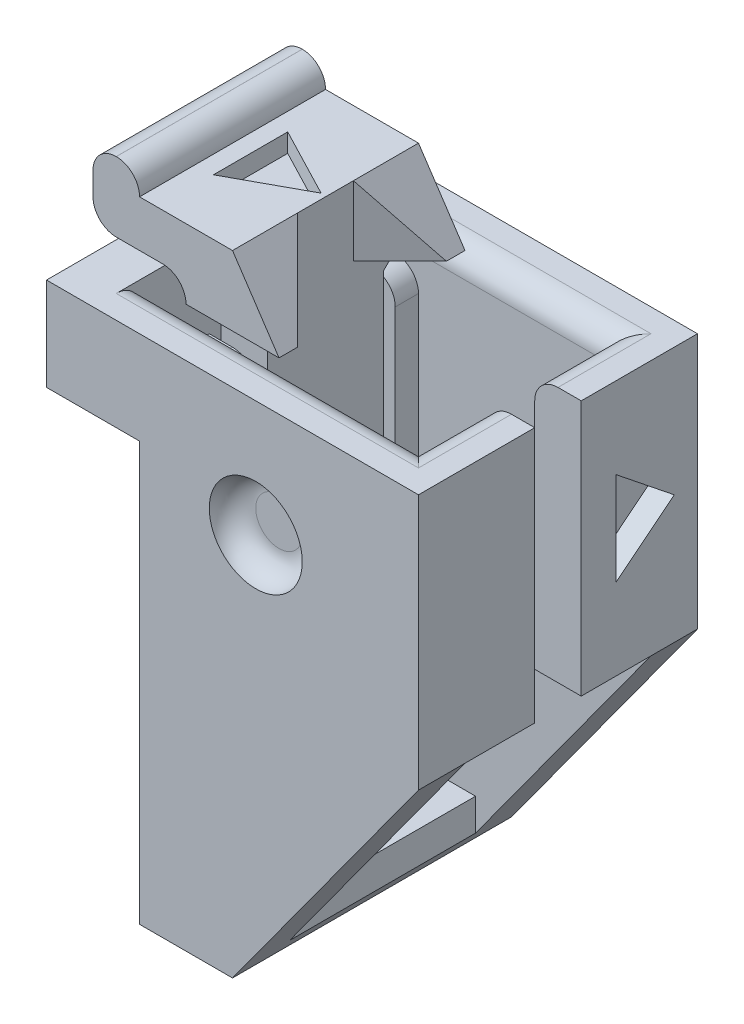
SolidWorks part; units mm, degrees
ref_plane "Front Plane" through (0, 0, 0) normal (0, 0, 1) x (1, 0, 0)
ref_plane "Top Plane" through (0, 0, 0) normal (0, 1, 0) x (1, 0, 0)
ref_plane "Right Plane" through (0, 0, 0) normal (1, 0, 0) x (0, 0, -1)
sketch "BaseSketch" plane through (0, 0, 0) normal (0, 1, 0) x (1, 0, 0)
  line L1 (-6.2677, 3.9685) -> (9.7323, 3.9685)
  line L2 (-6.2677, 3.9685) -> (-6.2677, -8.0315)
  line L3 (-6.2677, -8.0315) -> (9.7323, -8.0315)
  line L4 (9.7323, 3.9685) -> (9.7323, -8.0315)
  dimension "D1" = 16
  dimension "D2" = 12
extrude "BaseExtrude" add sketch "BaseSketch" along normal blind 2
sketch "SlotSketch" plane through (0, 2, 0) normal (0, 1, 0) x (1, 0, 0)
  line L10 (-2.2677, 0.9685) -> (-0.2677, 0.9685)
  line L11 (-2.2677, 1.9685) -> (-4.2677, 1.9685)
  line L12 (-2.2677, 1.9685) -> (-2.2677, 0.9685)
  line L13 (-0.2677, -6.0315) -> (7.7323, -6.0315)
  line L14 (7.7323, -6.0315) -> (7.7323, 1.9685)
  line L15 (-4.2677, -6.0315) -> (7.7323, -6.0315)
  line L16 (-4.2677, 1.9685) -> (-4.2677, -6.0315)
  line L17 (7.7323, 1.9685) -> (-4.2677, 1.9685)
  line L18 (7.7323, -6.0315) -> (7.7323, 1.9685)
  line L19 (-4.2677, -6.0315) -> (-2.2677, -6.0315)
  line L20 (-4.2677, 1.9685) -> (-4.2677, -6.0315)
  line L21 (7.7323, 1.9685) -> (-0.2677, 1.9685)
  line L22 (-0.2677, 1.9685) -> (-0.2677, 0.9685)
  line L23 (-2.2677, -5.0315) -> (-0.2677, -5.0315)
  line L24 (-2.2677, 0.4685) -> (-2.2677, -4.5315)
  line L25 (-2.2677, 0.4685) -> (-0.2677, 0.4685)
  line L26 (-2.2677, 0.4685) -> (-2.2677, -4.5315)
  line L27 (-2.2677, -4.5315) -> (-0.2677, -4.5315)
  line L28 (-0.2677, 0.4685) -> (-0.2677, -4.5315)
  line L29 (-0.2677, 0.4685) -> (-0.2677, -4.5315)
  line L30 (-2.2677, -5.0315) -> (-2.2677, -6.0315)
  line L31 (-0.2677, -5.0315) -> (-0.2677, -6.0315)
  line L33 (-6.2677, 3.9685) -> (9.7323, 3.9685)
  line L34 (-6.2677, 3.9685) -> (-6.2677, -8.0315)
  line L35 (-6.2677, -8.0315) -> (9.7323, -8.0315)
  line L36 (9.7323, 3.9685) -> (9.7323, -8.0315)
  line M5 (-6.2677, 3.9685) -> (-6.2677, -8.0315)
  line M6 (-6.2677, -8.0315) -> (9.7323, -8.0315)
  line M7 (9.7323, -8.0315) -> (9.7323, 3.9685)
  line M8 (9.7323, 3.9685) -> (-6.2677, 3.9685)
  dimension "D2" = 8
  dimension "D3" = 2
  dimension "D4" = 2
  dimension "D5" = 8
  dimension "D6" = 1
  dimension "D7" = 1
  dimension "D8" = 5
  dimension "D9" = 0.5
  dimension "D1" = 2
extrude "FlapExtrude" add sketch "SlotSketch" along normal blind 20.1 contours L25 L28 L27 L24
sketch "HandleBaseSketch" plane through (0, 22.1, 0) normal (0, 1, 0) x (1, 0, 0)
  line L0 (9.7323, 3.9685) -> (-6.2677, 3.9685) construction
  line L1 (-2.2677, 1.9685) -> (-0.2677, 1.9685)
  line L2 (-2.2677, 1.9685) -> (-2.2677, -6.0315)
  line L3 (-2.2677, -6.0315) -> (-0.2677, -6.0315)
  line L4 (-0.2677, 1.9685) -> (-0.2677, -6.0315)
  line L5 (-6.2677, -8.0315) -> (9.7323, -8.0315) construction
  dimension "D1" = 2
  dimension "D2" = 2
extrude "HandleBase" add sketch "HandleBaseSketch" along normal blind 3
sketch "TriangleBaseSketch" plane through (-0.2677, 0, 0) normal (1, 0, 0) x (0, 0, -1)
  line L0 (-6.0315, 22.1) -> (-3.2315, 22.1)
  line L1 (-3.2315, 22.1) -> (-3.2315, 25.1)
  line L2 (-6.0315, 25.1) -> (1.9685, 25.1) construction
  line L3 (-3.2315, 25.1) -> (-6.0315, 25.1)
  line L4 (-6.0315, 25.1) -> (-6.0315, 22.1)
  line L5 (1.9685, 22.1) -> (-0.8315, 22.1)
  line L6 (-0.8315, 22.1) -> (-0.8315, 25.1)
  line L7 (-0.8315, 25.1) -> (1.9685, 25.1)
  line L8 (1.9685, 25.1) -> (1.9685, 22.1)
extrude "PyramidExtrude" add sketch "TriangleBaseSketch" along normal blind 2.8
sketch "PyramidSideCutSketch" plane through (0, 0, -1.9685) normal (0, 0, -1) x (-1, 0, 0)
  line L0 (0.2677, 25.1) -> (0.2677, 22.1)
  line L1 (0.2677, 25.1) -> (-2.5323, 25.1)
  line L2 (-2.5323, 25.1) -> (-2.5323, 22.1)
  line L3 (-2.5323, 22.1) -> (-1.7323, 22.1)
  line L4 (-2.5323, 22.1) -> (2.2677, 22.1) construction
  line L5 (-1.7323, 22.1) -> (0.2677, 25.1)
  dimension "D1" = 2
sketch "PyramidTopCutSketch" plane through (0, 25.1, 0) normal (0, 1, 0) x (1, 0, 0)
  line L0 (-0.2677, -3.2315) -> (2.5323, -6.0315)
  line L1 (2.5323, -6.0315) -> (2.5323, -3.2315)
  line L2 (2.5323, -3.2315) -> (-0.2677, -3.2315)
  line L3 (-0.2677, -0.8315) -> (2.5323, 1.9685)
  line L4 (2.5323, 1.9685) -> (2.5323, -0.8315)
  line L5 (2.5323, -0.8315) -> (-0.2677, -0.8315)
extrude "PyramidTopCut" cut sketch "PyramidTopCutSketch" against normal blind 3
extrude "PyramidSideCut" cut sketch "PyramidSideCutSketch" against normal through all contours L1 L2 L3 L5
extrude "Boss-Extrude5" add sketch "SlotSketch<6>" along normal blind 3 contours L31 L23 L30 L19 L20 L11 L12 L10 L22 L21 L18 L13 M8 M5 M6 M7 | L12 L10 L22 L21 L18 L13 L31 L23 L30 L19 L20 L11 | L33 L36 L35 L34 region at (-1.2677, 2, -1.4685) region at (-1.2677, 2, 5.5315) region at (1.7323, 2, -3.7685)
sketch "SlotSketch<6>" plane through (0, 2, 0) normal (0, 1, 0) x (1, 0, 0) same geometry as "SlotSketch"
extrude "Sides" add sketch "SlotSketch<7>" along normal blind 20 contours L11 L20 L19 L30 L23 L31 L13 L18 L21 L22 L10 L12 | L33 L36 L35 L34
sketch "SlotSketch<7>" plane through (0, 2, 0) normal (0, 1, 0) x (1, 0, 0) same geometry as "SlotSketch"
sketch "Sketch7" plane through (-0.2677, 0, 0) normal (1, 0, 0) x (0, 0, -1)
  line L0 (-5.0315, 22) -> (-5.0315, 2) construction
  line L1 (-6.0315, 22) -> (-5.0315, 22)
  line L2 (-6.0315, 22) -> (-6.0315, 20.4974)
  line L3 (-6.0315, 20.4974) -> (-5.0315, 20.4974)
  line L4 (-5.0315, 22) -> (-5.0315, 20.4974)
  line L5 (1.9685, 22) -> (1.9685, 2) construction
  line L6 (0.9685, 22) -> (1.9685, 22)
  line L7 (0.9685, 22) -> (0.9685, 20.4974)
  line L8 (0.9685, 20.4974) -> (1.9685, 20.4974)
  line L9 (1.9685, 22) -> (1.9685, 20.4974)
extrude "WallClearanceCut" cut sketch "Sketch7" against normal blind 2
sketch "BaseTriangleCutSketch" plane through (0, 0, 8.0315) normal (0, 0, 1) x (1, 0, 0)
  line L0 (9.7323, 0) -> (1.7323, 0)
  line L1 (-6.2677, 0) -> (9.7323, 0) construction
  line L2 (1.7323, 0) -> (9.7323, 11)
  line L3 (9.7323, 22) -> (9.7323, 0) construction
  line L4 (9.7323, 11) -> (9.7323, 0)
extrude "BaseTriangleCut" cut sketch "BaseTriangleCutSketch" against normal through all
sketch "Sketch9" plane through (-2.2677, 0, 0) normal (-1, 0, 0) x (0, 0, 1)
  line L0 (6.0315, 25.1) -> (6.0315, 22.1) construction
  line L1 (-1.9685, 25.1) -> (6.0315, 25.1)
  line L2 (-1.9685, 25.1) -> (-1.9685, 23.1)
  line L3 (-1.9685, 23.1) -> (6.0315, 23.1)
  line L4 (6.0315, 25.1) -> (6.0315, 23.1)
extrude "Handle" add sketch "Sketch9" along normal blind 4
sketch "Sketch10" plane through (0, 25.1, 0) normal (0, 1, 0) x (1, 0, 0)
  line L0 (-0.2677, 1.9685) -> (-6.2677, 1.9685) construction
  line L1 (-6.2677, -6.0315) -> (-4.2659, -6.0315)
  line L2 (-6.2677, -6.0315) -> (-6.2677, 1.9685)
  line L3 (-6.2677, 1.9685) -> (-4.2659, 1.9685)
  line L4 (-4.2659, -6.0315) -> (-4.2659, 1.9685)
extrude "Boss-Extrude8" add sketch "Sketch10" along normal blind 1
sketch "WashHoleSketch" plane through (-6.2677, 0, 0) normal (-1, 0, 0) x (0, 0, 1)
  line L0 (-3.9685, 22) -> (-3.9685, 0) construction
  line L1 (-1.9685, 18) -> (6.0315, 18)
  line L2 (-1.9685, 18) -> (-1.9685, 4)
  line L3 (-1.9685, 4) -> (6.0315, 4)
  line L4 (6.0315, 18) -> (6.0315, 4)
  line L5 (8.0315, 22) -> (8.0315, 0) construction
  line L6 (-3.9685, 22) -> (8.0315, 22) construction
  line L7 (-3.9685, 0) -> (8.0315, 0) construction
  dimension "D1" = 2
  dimension "D2" = 2
  dimension "D3" = 4
  dimension "D4" = 4
extrude "WashHole" cut sketch "WashHoleSketch" against normal blind 2
fillet "Fillet1" radius 1 10 edges at (1.7323, 22, -1.9685) (1.7323, 22, 6.0315) (7.7323, 22, 2.0315) (-2.2677, 2, 2.0315) (-2.2677, 23.1, 2.0315) (-6.2677, 23.1, 2.0315) (-4.2659, 26.1, 2.0315) (-6.2677, 26.1, 2.0315) (-0.2677, 20.4974, -1.4685) (-0.2677, 20.4974, 5.5315)
sketch "MarkerSketch" plane through (0, 25.1, 0) normal (0, 1, 0) x (1, 0, 0)
  line L0 (-0.4994, -1.9893) -> (-3.4984, -0.4264)
  line L1 (-3.4984, -0.4264) -> (-3.4984, -3.6225)
  line L2 (-3.4984, -3.6225) -> (-0.4994, -1.9893)
extrude "Cut-Extrude6" cut sketch "MarkerSketch" against normal blind 0.8
sketch "Sketch11" plane through (7.7323, 0, 0) normal (-1, 0, 0) x (0, 0, 1)
  line L0 (-1.9685, 18) -> (-1.9685, 4) construction
  line L1 (-1.9685, 11) -> (6.0315, 11)
  line L2 (-1.9685, 11) -> (-1.9685, 8.25)
  line L3 (-1.9685, 8.25) -> (6.0315, 8.25)
  line L4 (6.0315, 11) -> (6.0315, 8.25)
extrude "Cut-Extrude7" cut sketch "Sketch11" against normal blind 10
sketch "Sketch12" plane through (0, 2, 0) normal (0, 1, 0) x (1, 0, 0)
  line L0 (-0.2677, -6.0315) -> (3.1868, -6.0315) construction
  line L1 (3.1868, 1.9685) -> (2.1868, 1.9685)
  line L2 (3.1868, 1.9685) -> (3.1868, -6.0315)
  line L3 (3.1868, -6.0315) -> (2.1868, -6.0315)
  line L4 (2.1868, 1.9685) -> (2.1868, -6.0315)
  dimension "D1" = 1
extrude "Cut-Extrude8" cut sketch "Sketch12" against normal blind 10
chamfer "Chamfer1" distance 1 angle 45 2 edges
sketch "Sketch14" plane through (0, 0, 8.0315) normal (0, 0, 1) x (1, 0, 0)
  line L0 (-6.2677, 0) -> (1.7323, 0) construction
  line L1 (-6.2677, 18) -> (-2.2677, 18)
  line L2 (-6.2677, 18) -> (-6.2677, 0)
  line L3 (-6.2677, 0) -> (-2.2677, 0)
  line L4 (-2.2677, 18) -> (-2.2677, 0)
extrude "Cut-Extrude9" cut sketch "Sketch14" against normal through all
sketch "Sketch15" plane through (9.7323, 0, 0) normal (1, 0, 0) x (0, 0, -1)
  line L0 (-2.0315, 22) -> (-2.0315, 11) construction
  line L1 (3.9685, 22) -> (-8.0315, 22) construction
  line L2 (1.9685, 11) -> (-6.0315, 11) construction
  line L4 (-1.0315, 22) -> (-3.0315, 22)
  line L5 (-1.0315, 22) -> (-1.0315, 11)
  line L6 (-1.0315, 11) -> (-3.0315, 11)
  line L7 (-3.0315, 22) -> (-3.0315, 11)
  point P10 (-2.0315, 22)
  dimension "D1" = 2
extrude "Cut-Extrude10" cut sketch "Sketch15" against normal blind 4
sketch "Sketch16" plane through (0, 0, 8.0315) normal (0, 0, 1) x (1, 0, 0)
  line L0 (-6.2677, 22) -> (9.7323, 22) construction
  line L1 (-2.2677, 0) -> (-2.2677, 18) construction
  circle A0 centre (2.7323, 17) radius 2
  dimension "D3" = 4
  dimension "D1" = 5
  dimension "D2" = 5
extrude "Cut-Extrude11" cut sketch "Sketch16" against normal blind 1
fillet "Fillet2" radius 1 1 edges at (4.7323, 17, 7.0315)
sketch "Sketch17" plane through (9.7323, 0, 0) normal (1, 0, 0) x (0, 0, -1)
  line L0 (0.4685, 14.5) -> (0.4685, 18.5)
  line L1 (0.4685, 18.5) -> (2.9685, 16.5)
  line L2 (2.9685, 16.5) -> (0.4685, 14.5)
  line L3 (-1.0315, 11) -> (-1.0315, 22) construction
  line L4 (3.9685, 22) -> (3.9685, 11) construction
  point P7 (-1.0315, 16.5)
  point P8 (0.4685, 16.5)
  dimension "D1" = 1.5
  dimension "D2" = 1
  dimension "D3" = 4
extrude "Cut-Extrude12" cut sketch "Sketch17" against normal blind 1
sketch "Sketch19" plane through (0, 0, -3.9685) normal (0, 0, -1) x (-1, 0, 0)
  line L1 (0.7677, 5) -> (0.7677, 17.1948) construction
  line L2 (-1.7323, 0) -> (2.2677, 0) construction
  line L3 (2.2677, 0) -> (2.2677, 18) construction
  text T0 "<b>LOW</b>" font "Arial" height in points 18
  dimension "D1" = 5
  dimension "D2" = 1.5
extrude "Cut-Extrude13" cut sketch "Sketch19" against normal blind 1
